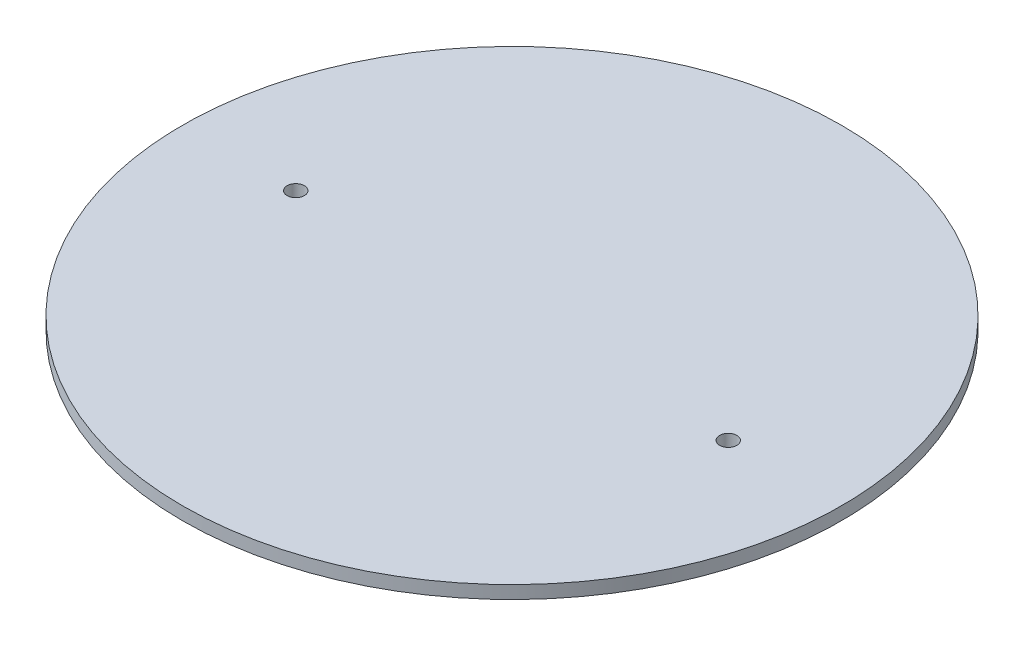
SolidWorks part; units mm, degrees
material "1060 Alloy"
ref_plane "Front Plane" through (0, 0, 0) normal (0, 0, 1) x (1, 0, 0)
ref_plane "Top Plane" through (0, 0, 0) normal (0, 1, 0) x (1, 0, 0)
ref_plane "Right Plane" through (0, 0, 0) normal (1, 0, 0) x (0, 0, -1)
sketch "Sketch1" plane through (0, 0, 0) normal (0, 1, 0) x (1, 0, 0)
  line L0 (-50, 0) -> (50, 0) construction
  circle A0 centre (0, 0) radius 76.2
  circle A1 centre (-50, 0) radius 2
  circle A2 centre (50, 0) radius 2
  dimension "D1" = 152.4
  dimension "D2" = 4
  dimension "D3" = 4
  dimension "D4" = 100
extrude "Boss-Extrude1" add sketch "Sketch1" along normal blind 1.5 and the other way blind 1.5
